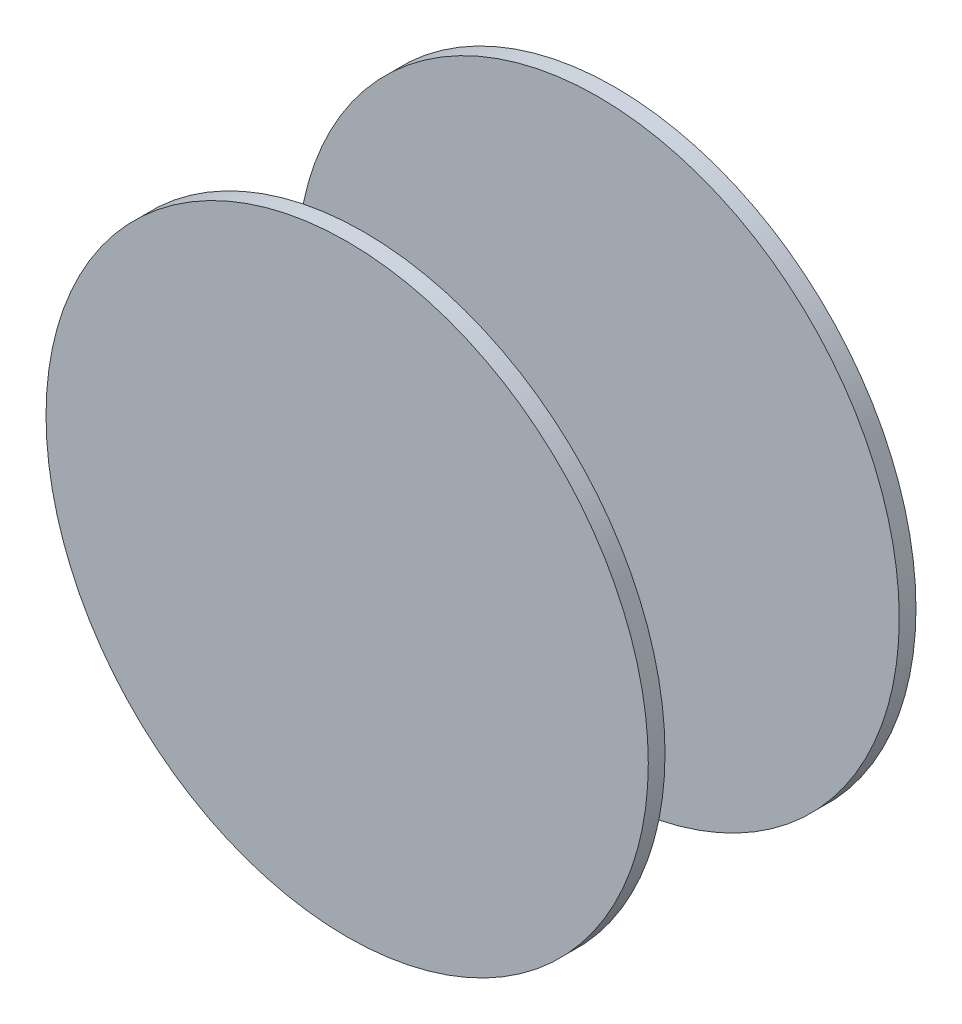
SolidWorks part; units mm, degrees
material "1023 Carbon Steel Sheet (SS)"
ref_plane "Front Plane" through (0, 0, 0) normal (0, 0, 1) x (1, 0, 0)
ref_plane "Top Plane" through (0, 0, 0) normal (0, 1, 0) x (1, 0, 0)
ref_plane "Right Plane" through (0, 0, 0) normal (1, 0, 0) x (0, 0, -1)
sketch "Sketch1" plane through (0, 0, 0) normal (0, 0, 1) x (1, 0, 0)
  circle A0 centre (0, 0) radius 45
extrude "Boss-Extrude1" add sketch "Sketch1" along normal mid plane 40
extrude "Cut-Extrude1" cut sketch "Sketch1<2>" against normal mid plane 35
sketch "Sketch1<2>" plane through (0, 0, 0) normal (0, 0, 1) x (1, 0, 0) same geometry as "Sketch1"
